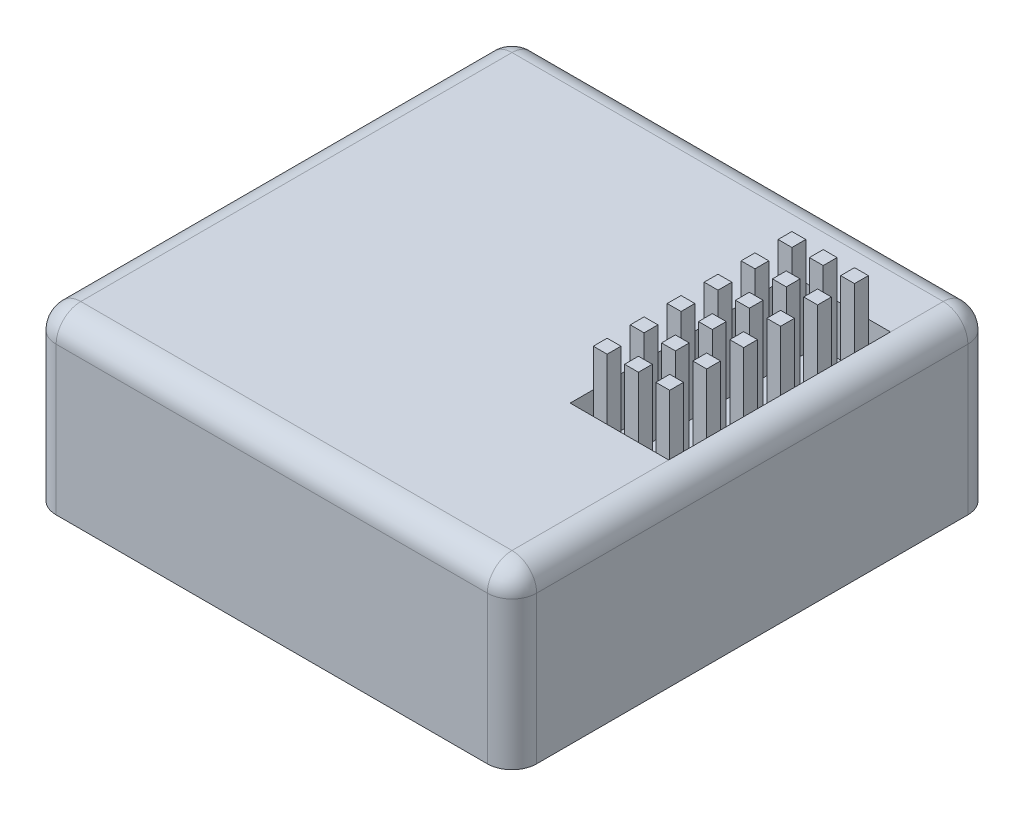
SolidWorks part; units mm, degrees
ref_plane "Front" through (0, 0, 0) normal (0, 0, 1) x (1, 0, 0)
ref_plane "Top" through (0, 0, 0) normal (0, 1, 0) x (1, 0, 0)
ref_plane "Right" through (0, 0, 0) normal (1, 0, 0) x (0, 0, -1)
sketch "Sketch1" plane through (0, 0, 0) normal (0, 1, 0) x (1, 0, 0)
  line L1 (-19.5, 19.5) -> (19.5, 19.5)
  line L2 (-19.5, 19.5) -> (-19.5, -19.5)
  line L3 (-19.5, -19.5) -> (19.5, -19.5)
  line L4 (19.5, 19.5) -> (19.5, -19.5)
  line L5 (-19.5, 19.5) -> (19.5, -19.5) construction
  line L6 (-19.5, -19.5) -> (19.5, 19.5) construction
  point P0 (0, 0)
  dimension "D1" = 39
  dimension "D2" = 39
extrude "Boss-Extrude1" add sketch "Sketch1" along normal blind 14
fillet "Fillet1" radius 2 4 edges at (-19.5, 7, 19.5) (-19.5, 7, -19.5) (19.5, 7, -19.5) (19.5, 7, 19.5)
fillet "Fillet2" radius 2 8 edges at (-18.9142, 14, -18.9142) (0, 14, -19.5) (18.9142, 14, -18.9142) (19.5, 14, 0) (18.9142, 14, 18.9142) (0, 14, 19.5) (-18.9142, 14, 18.9142) (-19.5, 14, 0)
sketch "Sketch2" plane through (0, 14, 0) normal (0, 1, 0) x (1, 0, 0)
  line L0 (17.5, -17.5) -> (17.5, 17.5) construction
  line L1 (17.5, 13.2207) -> (9.5, 13.2207)
  line L2 (17.5, 13.2207) -> (17.5, -4.7793)
  line L3 (17.5, -4.7793) -> (9.5, -4.7793)
  line L4 (9.5, 13.2207) -> (9.5, -4.7793)
  line L5 (14.1015, 12.2822) -> (14.1015, 11.1592)
  line L6 (10.4385, 12.2822) -> (11.5615, 12.2822)
  line L7 (10.4385, 12.2822) -> (10.4385, 11.1592)
  line L8 (10.4385, 11.1592) -> (11.5615, 11.1592)
  line L9 (11.5615, 12.2822) -> (11.5615, 11.1592)
  line L10 (10.4385, 12.2822) -> (11.5615, 11.1592) construction
  line L11 (10.4385, 11.1592) -> (11.5615, 12.2822) construction
  line L12 (12.9785, 11.1592) -> (14.1015, 11.1592)
  line L13 (12.9785, 12.2822) -> (12.9785, 11.1592)
  line L14 (12.9785, 12.2822) -> (14.1015, 12.2822)
  line L15 (16.6415, 12.2822) -> (16.6415, 11.1592)
  line L16 (15.5185, 11.1592) -> (16.6415, 11.1592)
  line L17 (15.5185, 12.2822) -> (15.5185, 11.1592)
  line L18 (15.5185, 12.2822) -> (16.6415, 12.2822)
  line L19 (10.4385, 9.2822) -> (10.4385, 8.1592)
  line L20 (10.4385, 9.2822) -> (11.5615, 9.2822)
  line L21 (10.4385, 9.2822) -> (11.5615, 8.1592) construction
  line L22 (10.4385, 8.1592) -> (11.5615, 8.1592)
  line L23 (11.5615, 9.2822) -> (11.5615, 8.1592)
  line L24 (12.9785, 9.2822) -> (14.1015, 9.2822)
  line L25 (12.9785, 9.2822) -> (12.9785, 8.1592)
  line L26 (14.1015, 9.2822) -> (14.1015, 8.1592)
  line L27 (12.9785, 8.1592) -> (14.1015, 8.1592)
  line L28 (15.5185, 9.2822) -> (15.5185, 8.1592)
  line L29 (15.5185, 9.2822) -> (16.6415, 9.2822)
  line L30 (16.6415, 9.2822) -> (16.6415, 8.1592)
  line L31 (15.5185, 8.1592) -> (16.6415, 8.1592)
  line L32 (10.4385, 6.2822) -> (10.4385, 5.1592)
  line L33 (10.4385, 6.2822) -> (11.5615, 6.2822)
  line L34 (10.4385, 6.2822) -> (11.5615, 5.1592) construction
  line L35 (10.4385, 5.1592) -> (11.5615, 5.1592)
  line L36 (11.5615, 6.2822) -> (11.5615, 5.1592)
  line L37 (12.9785, 6.2822) -> (14.1015, 6.2822)
  line L38 (12.9785, 6.2822) -> (12.9785, 5.1592)
  line L39 (14.1015, 6.2822) -> (14.1015, 5.1592)
  line L40 (12.9785, 5.1592) -> (14.1015, 5.1592)
  line L41 (15.5185, 6.2822) -> (15.5185, 5.1592)
  line L42 (15.5185, 6.2822) -> (16.6415, 6.2822)
  line L43 (16.6415, 6.2822) -> (16.6415, 5.1592)
  line L44 (15.5185, 5.1592) -> (16.6415, 5.1592)
  line L45 (10.4385, 3.2822) -> (10.4385, 2.1592)
  line L46 (10.4385, 3.2822) -> (11.5615, 3.2822)
  line L47 (10.4385, 3.2822) -> (11.5615, 2.1592) construction
  line L48 (10.4385, 2.1592) -> (11.5615, 2.1592)
  line L49 (11.5615, 3.2822) -> (11.5615, 2.1592)
  line L50 (12.9785, 3.2822) -> (14.1015, 3.2822)
  line L51 (12.9785, 3.2822) -> (12.9785, 2.1592)
  line L52 (14.1015, 3.2822) -> (14.1015, 2.1592)
  line L53 (12.9785, 2.1592) -> (14.1015, 2.1592)
  line L54 (15.5185, 3.2822) -> (15.5185, 2.1592)
  line L55 (15.5185, 3.2822) -> (16.6415, 3.2822)
  line L56 (16.6415, 3.2822) -> (16.6415, 2.1592)
  line L57 (15.5185, 2.1592) -> (16.6415, 2.1592)
  line L58 (10.4385, 0.2822) -> (10.4385, -0.8408)
  line L59 (10.4385, 0.2822) -> (11.5615, 0.2822)
  line L60 (10.4385, 0.2822) -> (11.5615, -0.8408) construction
  line L61 (10.4385, -0.8408) -> (11.5615, -0.8408)
  line L62 (11.5615, 0.2822) -> (11.5615, -0.8408)
  line L63 (12.9785, 0.2822) -> (14.1015, 0.2822)
  line L64 (12.9785, 0.2822) -> (12.9785, -0.8408)
  line L65 (14.1015, 0.2822) -> (14.1015, -0.8408)
  line L66 (12.9785, -0.8408) -> (14.1015, -0.8408)
  line L67 (15.5185, 0.2822) -> (15.5185, -0.8408)
  line L68 (15.5185, 0.2822) -> (16.6415, 0.2822)
  line L69 (16.6415, 0.2822) -> (16.6415, -0.8408)
  line L70 (15.5185, -0.8408) -> (16.6415, -0.8408)
  line L71 (10.4385, -2.7178) -> (10.4385, -3.8408)
  line L72 (10.4385, -2.7178) -> (11.5615, -2.7178)
  line L73 (10.4385, -2.7178) -> (11.5615, -3.8408) construction
  line L74 (10.4385, -3.8408) -> (11.5615, -3.8408)
  line L75 (11.5615, -2.7178) -> (11.5615, -3.8408)
  line L76 (12.9785, -2.7178) -> (14.1015, -2.7178)
  line L77 (12.9785, -2.7178) -> (12.9785, -3.8408)
  line L78 (14.1015, -2.7178) -> (14.1015, -3.8408)
  line L79 (12.9785, -3.8408) -> (14.1015, -3.8408)
  line L80 (15.5185, -2.7178) -> (15.5185, -3.8408)
  line L81 (15.5185, -2.7178) -> (16.6415, -2.7178)
  line L82 (16.6415, -2.7178) -> (16.6415, -3.8408)
  line L83 (15.5185, -3.8408) -> (16.6415, -3.8408)
  point P6 (11, 11.7207)
  point P11 (11, -3.2793)
  dimension "D1" = 1.5
  dimension "D2" = 1.5
  dimension "D3" = 8
  dimension "D4" = 18
  dimension "D7" = 1.5
  dimension "D5" = 3
  dimension "D6" = 6
extrude "Cut-Extrude1" cut sketch "Sketch2" against normal blind 4
extrude "Boss-Extrude3" add sketch "Sketch2<2>" along normal blind 4 contours L13 L12 L5 L14 | L9 L8 L7 L6 | L22 L23 L20 L19 | L28 L31 L30 L29 | L16 L15 L18 L17 | L27 L26 L24 L25 | L40 L39 L37 L38 | L35 L36 L33 L32 | L48 L49 L46 L45 | L53 L52 L50 L51 | L57 L56 L55 L54 | L44 L43 L42 L41 | L68 L69 L70 L67 | L63 L65 L66 L64 | L59 L62 L61 L58 | L72 L75 L74 L71 | L76 L78 L79 L77 | L81 L82 L83 L80
sketch "Sketch2<2>" plane through (0, 14, 0) normal (0, 1, 0) x (1, 0, 0) same geometry as "Sketch2"
sketch "Sketch3" plane through (-19.5, 0, 0) normal (-1, 0, 0) x (0, 0, 1)
  line L0 (17.5, 12) -> (-17.5, 12) construction
  line L1 (-3.8801, 12) -> (3.1199, 12)
  line L2 (-3.8801, 12) -> (-3.8801, 9)
  line L3 (-3.8801, 9) -> (3.1199, 9)
  line L4 (3.1199, 12) -> (3.1199, 9)
  line L5 (-3.8801, 9) -> (3.1199, 12) construction
  point P6 (-0.3801, 10.5)
  point P7 (-0.3801, 12)
  dimension "D1" = 3
  dimension "D2" = 7
extrude "Cut-Extrude2" cut sketch "Sketch3" against normal blind 2
